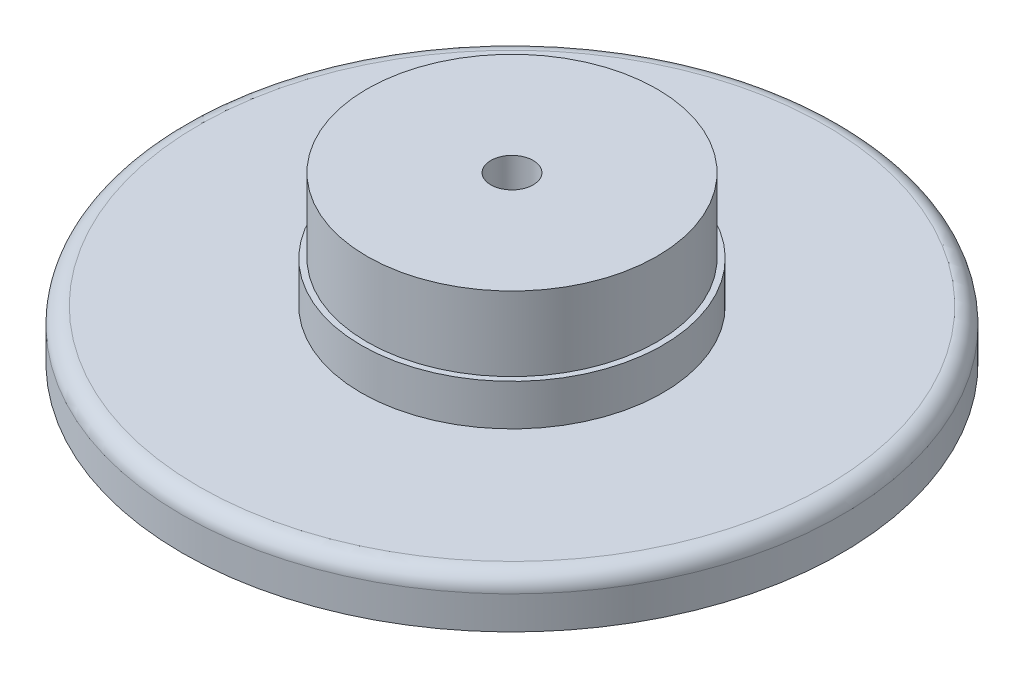
SolidWorks part; units mm, degrees
ref_plane "Front Plane" through (0, 0, 0) normal (0, 0, 1) x (1, 0, 0)
ref_plane "Top Plane" through (0, 0, 0) normal (0, 1, 0) x (1, 0, 0)
ref_plane "Right Plane" through (0, 0, 0) normal (1, 0, 0) x (0, 0, -1)
sketch "Sketch1" plane through (0, 0, 0) normal (0, 1, 0) x (1, 0, 0)
  circle A0 centre (0, 0) radius 22.352
  circle A1 centre (0, 0) radius 23.241
  circle A2 centre (0, 0) radius 50.8
  dimension "D1" = 46.482
  dimension "D2" = 101.6
  dimension "D3" = 44.704
extrude "Boss-Extrude4" add sketch "Sketch1" along normal blind 7.62 contours A2 A1 region at (-49.3632, 0, 0)
extrude "Boss-Extrude5" add sketch "Sketch1<6>" along normal blind 13.97 contours A1 A0 region at (-22.5836, 0, 0)
sketch "Sketch1<6>" plane through (0, 0, 0) normal (0, 1, 0) x (1, 0, 0) same geometry as "Sketch1"
extrude "Boss-Extrude6" add sketch "Sketch1<7>" along normal blind 25.4 contours A0 region at (0, 0, 0)
sketch "Sketch1<7>" plane through (0, 0, 0) normal (0, 1, 0) x (1, 0, 0) same geometry as "Sketch1"
hole_wizard "CSK for 1/4 Flat Head Machine Screw (100)1" positions "Sketch4" profile "Sketch5" countersink size "1/4" standard "ANSI Inch" end condition through all
sketch "Sketch4" plane through (0, 0, 0) normal (0, -1, 0) x (-1, 0, 0)
  point P0 (0, 0)
sketch "Sketch5" plane through (0, 0, 0) normal (1, 0, 0) x (0, 0, -1)
  line L0 (0, 0) -> (0, 25.4)
  line L1 (0, 25.4) -> (3.2639, 25.4)
  line L2 (3.2639, 25.4) -> (3.2639, 2.6641)
  line L3 (3.2639, 2.6641) -> (6.4389, 0)
  line L5 (6.4389, 0) -> (0, 0)
  line L6 (-3.2639, 2.6641) -> (-6.4389, 0) construction
  line L11 (0, -6.35) -> (0, 107.95) construction
  dimension "Thru Hole Dia." = 6.5278
  dimension "Thru Hole Depth" = 25.4
  dimension "Near C'Sink Dia." = 12.8778
  dimension "Near C'Sink Angle" = 100
fillet "Fillet1" [suppressed] radius 15.875
fillet "Fillet2" [suppressed] radius 15.875
fillet "Fillet3" radius 2.54 1 edges at (0, 7.62, 50.8)
